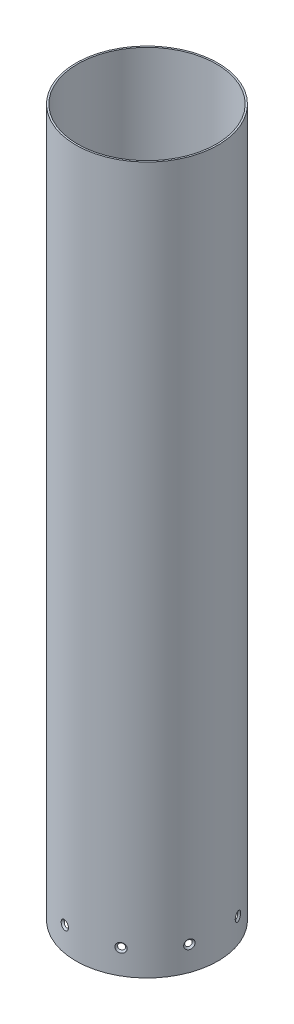
SolidWorks part; units mm, degrees
material "E-Glass Fiber"
ref_plane "Front Plane" through (0, 0, 0) normal (0, 0, 1) x (1, 0, 0)
ref_plane "Top Plane" through (0, 0, 0) normal (0, 1, 0) x (1, 0, 0)
ref_plane "Right Plane" through (0, 0, 0) normal (1, 0, 0) x (0, 0, -1)
sketch "Sketch1" plane through (0, 0, 0) normal (0, 1, 0) x (1, 0, 0)
  circle A0 centre (0, 0) radius 87
  circle A1 centre (0, 0) radius 85
extrude "Boss-Extrude1" add sketch "Sketch1" along normal blind 865
ref_plane "Plane2" through (0, 30, 0) normal (0, -1, 0) x (-1, 0, 0)
ref_plane "Plane1" through (-87, 0, 0) normal (-1, 0, 0) x (0, 0, 1)
sketch "Sketch2" plane through (-87, 0, 0) normal (-1, 0, 0) x (0, 0, 1)
  line L0 (-87, 0) -> (87, 0) construction
  circle A0 centre (0, 30) radius 2.75
  dimension "D1" = 30
extrude "Cut-Extrude1" cut sketch "Sketch2" against normal up to next
sketch "Sketch4" plane through (0, 30, 0) normal (0, -1, 0) x (1, 0, 0)
  line L1 (-93.9937, 0) -> (-74.5658, 0) construction
  line L6 (-86.3554, 0) -> (-86.3554, -5) construction
  line L7 (-86.3554, -5) -> (-81.3554, 0)
  line L8 (-86.3554, 0) -> (-81.3554, 0)
  line L9 (-86.3554, -5) -> (-87.969, -6.6136)
  line L10 (-87.969, -6.6136) -> (-87.969, 0)
  line L11 (-87.969, 0) -> (-86.3554, 0)
  circle A1 centre (0, 0) radius 86.5 construction
revolve "Cut-Revolve1" cut sketch "Sketch4" angle 360 about L1
pattern_circular "CirPattern1" count 9 over 360 about axis through (0, 0, 0) along (0, 1, 0) of "Cut-Revolve1"
